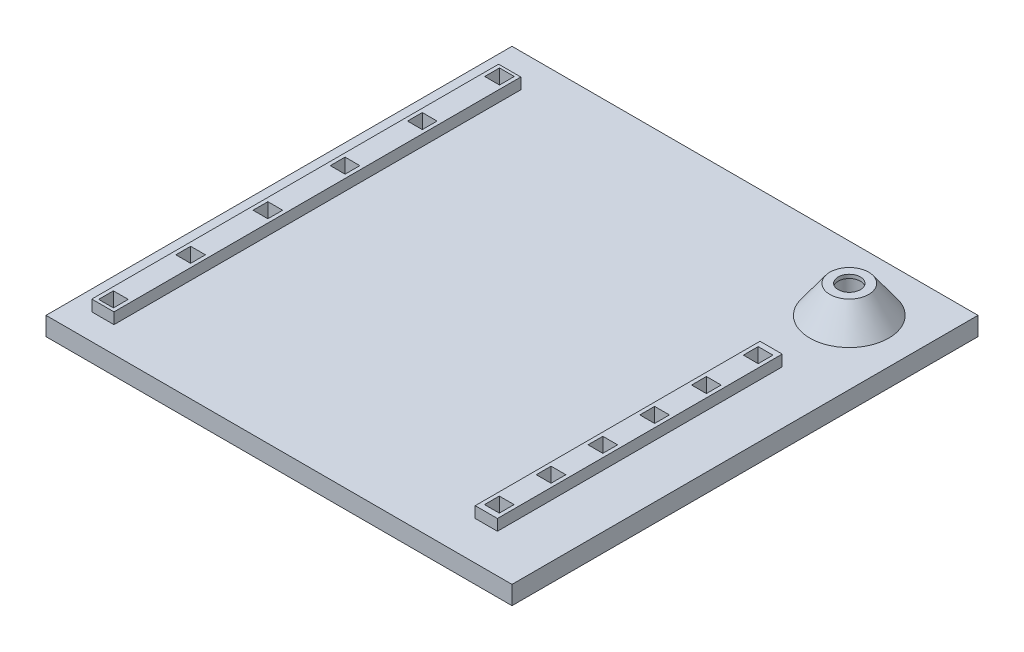
SolidWorks part; units mm, degrees
ref_plane "Front Plane" through (0, 0, 0) normal (0, 0, 1) x (1, 0, 0)
ref_plane "Top Plane" through (0, 0, 0) normal (0, 1, 0) x (1, 0, 0)
ref_plane "Right Plane" through (0, 0, 0) normal (1, 0, 0) x (0, 0, -1)
sketch "Sketch1" plane through (0, 0, 0) normal (0, 1, 0) x (1, 0, 0)
  line L1 (0, 0) -> (126, 0)
  line L2 (0, 0) -> (0, 126)
  line L3 (0, 126) -> (126, 126)
  line L4 (126, 0) -> (126, 126)
  dimension "D1" = 126
  dimension "D2" = 126
extrude "Boss-Extrude1" add sketch "Sketch1" along normal blind 5
sketch "Sketch3" plane through (0, 5, 0) normal (0, 1, 0) x (1, 0, 0)
  line L0 (108.6, 121.1) -> (108.6, 96.1) construction
  circle A0 centre (108.6, 108.6) radius 12.5
extrude "Boss-Extrude2" add sketch "Sketch3" along normal blind 7.5
sketch "Sketch4" plane through (0, 0, 0) normal (0, -1, 0) x (1, 0, 0)
  circle A1 centre (108.6, -108.6) radius 3.45
  dimension "D1" = 6.9
extrude "Cut-Extrude1" cut sketch "Sketch4" against normal blind 11.5
sketch "Sketch6" plane through (0, 12.5, 0) normal (0, 1, 0) x (1, 0, 0)
  line L0 (108.6, 121.1) -> (108.6, 96.1) construction
  circle A0 centre (108.6, 108.6) radius 12.5 construction
  circle A1 centre (108.6, 108.6) radius 3
  dimension "D1" = 6
extrude "Cut-Extrude2" cut sketch "Sketch6" against normal through all
chamfer "Chamfer1" distance 10 angle 36 1 edges at (108.6, 12.5, -96.1) first distance on face at (108.6, 12.5, -96.1)
sketch "Sketch9" plane through (0, 5, 0) normal (0, 1, 0) x (1, 0, 0)
  line L1 (111.6, 10.4582) -> (105.6, 10.4582)
  line L2 (0, 0) -> (126, 0) construction
  line L3 (111.6, 10.4582) -> (111.6, 87.4582)
  line L4 (108.6, 97.9164) -> (108.6, 0)
  line L5 (111.6, 87.4582) -> (105.6, 87.4582)
  line L6 (105.6, 10.4582) -> (105.6, 87.4582)
  line L7 (111.6, 10.4582) -> (105.6, 87.4582) construction
  line L8 (111.6, 87.4582) -> (105.6, 10.4582) construction
  circle A0 centre (108.6, 108.6) radius 10.6836 construction
  point P0 (108.6, 48.9582)
  point P5 (115.3692, 53.7951)
  dimension "D1" = 77
  dimension "D2" = 6
extrude "Boss-Extrude4" add sketch "Sketch9" along normal blind 3 contours L3 L5 L6 L1
sketch "Sketch10" plane through (0, 8, 0) normal (0, 1, 0) x (1, 0, 0)
  line L0 (108.6, 87.4582) -> (108.6, 10.4582) construction
  line L1 (111.6, 87.4582) -> (105.6, 87.4582) construction
  line L2 (111.6, 10.4582) -> (105.6, 10.4582) construction
  line L9 (110.6, 81.9582) -> (106.6, 81.9582)
  line L10 (110.6, 81.9582) -> (110.6, 85.9582)
  line L11 (110.6, 85.9582) -> (106.6, 85.9582)
  line L12 (106.6, 81.9582) -> (106.6, 85.9582)
  line L13 (110.6, 81.9582) -> (106.6, 85.9582) construction
  line L14 (110.6, 85.9582) -> (106.6, 81.9582) construction
  line L18 (110.6, 67.9589) -> (110.6, 71.9589)
  line L19 (110.6, 71.9589) -> (106.6, 71.9589)
  line L20 (106.6, 67.9589) -> (106.6, 71.9589)
  line L21 (110.6, 67.9589) -> (106.6, 67.9589)
  line L22 (110.6, 53.9597) -> (110.6, 57.9597)
  line L23 (110.6, 57.9597) -> (106.6, 57.9597)
  line L24 (106.6, 53.9597) -> (106.6, 57.9597)
  line L25 (110.6, 53.9597) -> (106.6, 53.9597)
  line L26 (110.6, 39.9604) -> (110.6, 43.9604)
  line L27 (110.6, 43.9604) -> (106.6, 43.9604)
  line L28 (106.6, 39.9604) -> (106.6, 43.9604)
  line L29 (110.6, 39.9604) -> (106.6, 39.9604)
  line L30 (110.6, 25.9612) -> (110.6, 29.9612)
  line L31 (110.6, 29.9612) -> (106.6, 29.9612)
  line L32 (106.6, 25.9612) -> (106.6, 29.9612)
  line L33 (110.6, 25.9612) -> (106.6, 25.9612)
  line L34 (110.6, 11.9619) -> (110.6, 15.9619)
  line L35 (110.6, 15.9619) -> (106.6, 15.9619)
  line L36 (106.6, 11.9619) -> (106.6, 15.9619)
  line L37 (110.6, 11.9619) -> (106.6, 11.9619)
  point P13 (108.6, 83.9582)
  dimension "D2" = 4
  dimension "D3" = 4
  dimension "D4" = 6
extrude "Cut-Extrude4" cut sketch "Sketch10" against normal through all
sketch "Sketch11" plane through (0, 5, 0) normal (0, 1, 0) x (1, 0, 0)
  line L5 (8.3811, 125) -> (8.3811, -1) construction
  line L7 (11.3811, 7) -> (5.3811, 7)
  line L8 (11.3811, 7) -> (11.3811, 117)
  line L9 (11.3811, 117) -> (5.3811, 117)
  line L10 (5.3811, 7) -> (5.3811, 117)
  line L11 (11.3811, 7) -> (5.3811, 117) construction
  line L12 (11.3811, 117) -> (5.3811, 7) construction
  point P9 (8.3811, 62)
  dimension "D1" = 110
  dimension "D2" = 6
extrude "Boss-Extrude5" add sketch "Sketch11" along normal blind 3
sketch "Sketch12" plane through (0, 8, 0) normal (0, 1, 0) x (1, 0, 0)
  line L0 (8.3811, 117) -> (8.3811, 7) construction
  line L5 (8.3811, 117.4103) -> (8.3811, 111.0629) construction
  line L6 (11.3811, 117) -> (5.3811, 117) construction
  line L7 (10.3811, 112.2366) -> (6.3811, 112.2366)
  line L8 (10.3811, 112.2366) -> (10.3811, 116.2366)
  line L9 (10.3811, 116.2366) -> (6.3811, 116.2366)
  line L10 (6.3811, 112.2366) -> (6.3811, 116.2366)
  line L11 (10.3811, 112.2366) -> (6.3811, 116.2366) construction
  line L12 (10.3811, 116.2366) -> (6.3811, 112.2366) construction
  line L17 (10.3811, 95.3589) -> (6.3811, 95.3589)
  line L18 (6.3811, 91.3589) -> (6.3811, 95.3589)
  line L19 (10.3811, 91.3589) -> (6.3811, 91.3589)
  line L20 (10.3811, 91.3589) -> (10.3811, 95.3589)
  line L21 (10.3811, 74.4812) -> (6.3811, 74.4812)
  line L22 (6.3811, 70.4812) -> (6.3811, 74.4812)
  line L23 (10.3811, 70.4812) -> (6.3811, 70.4812)
  line L24 (10.3811, 70.4812) -> (10.3811, 74.4812)
  line L25 (10.3811, 53.6035) -> (6.3811, 53.6035)
  line L26 (6.3811, 49.6035) -> (6.3811, 53.6035)
  line L27 (10.3811, 49.6035) -> (6.3811, 49.6035)
  line L28 (10.3811, 49.6035) -> (10.3811, 53.6035)
  line L29 (10.3811, 32.7258) -> (6.3811, 32.7258)
  line L30 (6.3811, 28.7258) -> (6.3811, 32.7258)
  line L31 (10.3811, 28.7258) -> (6.3811, 28.7258)
  line L32 (10.3811, 28.7258) -> (10.3811, 32.7258)
  line L33 (10.3811, 11.8481) -> (6.3811, 11.8481)
  line L34 (6.3811, 7.8481) -> (6.3811, 11.8481)
  line L36 (10.3811, 7.8481) -> (10.3811, 11.8481)
  line L37 (5.3811, 7) -> (11.3811, 7) construction
  line L43 (6.3811, 7.8481) -> (10.3811, 7.8481)
  line L47 (10.3811, 7.8481) -> (6.3811, 7.8481) [skipped]
  point P6 (8.3811, 114.2366)
  point P9 (8.3811, 114.2366)
  dimension "D2" = 4
  dimension "D3" = 4
  dimension "D4" = 6
extrude "Cut-Extrude5" cut sketch "Sketch12" against normal through all
